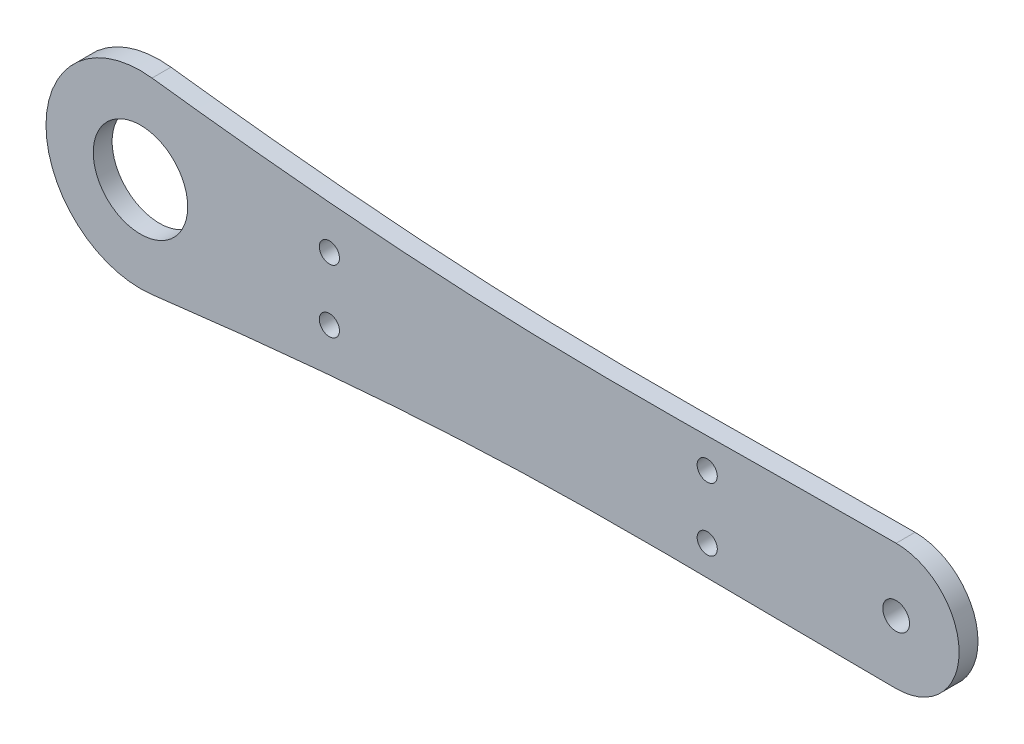
SolidWorks part; units mm, degrees
ref_plane "Front Plane" through (0, 0, 0) normal (0, 0, 1) x (1, 0, 0)
ref_plane "Top Plane" through (0, 0, 0) normal (0, 1, 0) x (1, 0, 0)
ref_plane "Right Plane" through (0, 0, 0) normal (1, 0, 0) x (0, 0, -1)
sketch "Sketch1" plane through (0, 0, 0) normal (0, 0, 1) x (1, 0, 0)
  line L0 (-103.1351, 0) -> (103.1351, 0) construction
  line L3 (0, 10) -> (0, -10) construction
  circle A2 centre (-60, 0) radius 7.5
  circle A3 centre (60, 0) radius 2.125
  arc A4 (-58.1622, 14.887) -> (-58.1622, -14.887) centre (-60, 0) ccw
  arc A5 (60, -10) -> (60, 10) centre (60, 0) ccw
  circle A6 centre (-30, 5) radius 1.6
  circle A7 centre (30, 5) radius 1.6
  circle A8 centre (30, -5) radius 1.6
  circle A9 centre (-30, -5) radius 1.6
  spline S0 degree 3 poles (60, 10) (39.9389, 10) (0.5184, 8.7165) (-38.8032, 12.4971) (-58.1622, 14.887) knots 0 0 0 0 0.506898 1 1 1 1
  spline S1 degree 3 poles (60, -10) (39.9389, -10) (0.5184, -8.7165) (-38.8032, -12.4971) (-58.1622, -14.887) knots 0 0 0 0 0.506898 1 1 1 1
  point P7 (0, 0)
  dimension "D3" = 15
  dimension "D1" = 4.25
  dimension "D2" = 30
  dimension "D4" = 20
  dimension "D10" = 3.2
  dimension "D5" = 120
  dimension "D6" = 20
  dimension "D7" = 60
  dimension "D8" = 30
  dimension "D9" = 5
  dimension "D14" = 30
  dimension "D15" = 5
  dimension "D12" = 2
  dimension "D13" = 2
extrude "Boss-Extrude1" add sketch "Sketch1" along normal blind 3
equation "\"L1\"= 120mm'Upper arm"
equation "\"L3\"= 75mm'Wrist→TCP"
equation "\"h0\"= 75mm'Shoulder height"
equation "\"t_link\"= 3mm'Link plate thickness"
equation "\"t_bracket\"= 4mm'Bracket thickness"
equation "\"d_pin\"= 4mm'Pin diameter (M4)"
equation "\"c_fit\"= 0.2mm'Nominal clearance - measured PLA 2026-10-01"
equation "\"L2\"= 120mm'Forearm"
equation "\"c_fit_pivot\"= \"c_fit\" + 0.05mm'Gripper pivot clearance - chosen 0.25 mm 2026-10-01"
equation "\"d_pin_gripper\"= 3mm'Gripper pivot diameter"
equation "\"w_link\"= 20mm'Link plate depth (bending direction)"
equation "\"w_gap\"= 20mm'Twin-plate gap - provisional, set by elbow servo mount"
equation "\"D1@Boss-Extrude1\"=\"t_link\""
equation "\"d_boss\"= 13mm'MG996R output boss dia - from downloaded model, verify with calipers"
equation "\"c_boss\"= 1mm'Radial clearance around servo boss"
equation "\"d_servo_hole\"= \"d_boss\" + 2 * \"c_boss\"'Plate clearance hole for servo boss (15 mm)"
equation "\"t_rim\"= 7.5mm'Min material around servo hole (M3 bolt ring + edge)"
equation "\"w_link_end\"= \"d_servo_hole\" + 2 * \"t_rim\"'Link plate end width at servo end (30 mm)"
equation "\"d_hole_m3\"= \"d_pin_gripper\" + \"c_fit\"'M3 bolt clearance hole (spacer and adapter bolts)"
equation "\"d_hole_pivot\"= \"d_pin\" + \"c_fit_pivot\"'M4 pivot hole where the pin rotates (4.25 mm)"
equation "\"D3@Sketch1\"=\"d_servo_hole\""
equation "\"D1@Sketch1\"=\"d_pin\"+\"c_fit_pivot\""
equation "\"D2@Sketch1\"=\"w_link_end\""
equation "\"D4@Sketch1\"=\"w_link\""
equation "\"D5@Sketch1\"=\"L1\""
equation "\"D6@Sketch1\"=\"w_link\""
equation "\"D10@Sketch1\"=\"d_hole_m3\""
